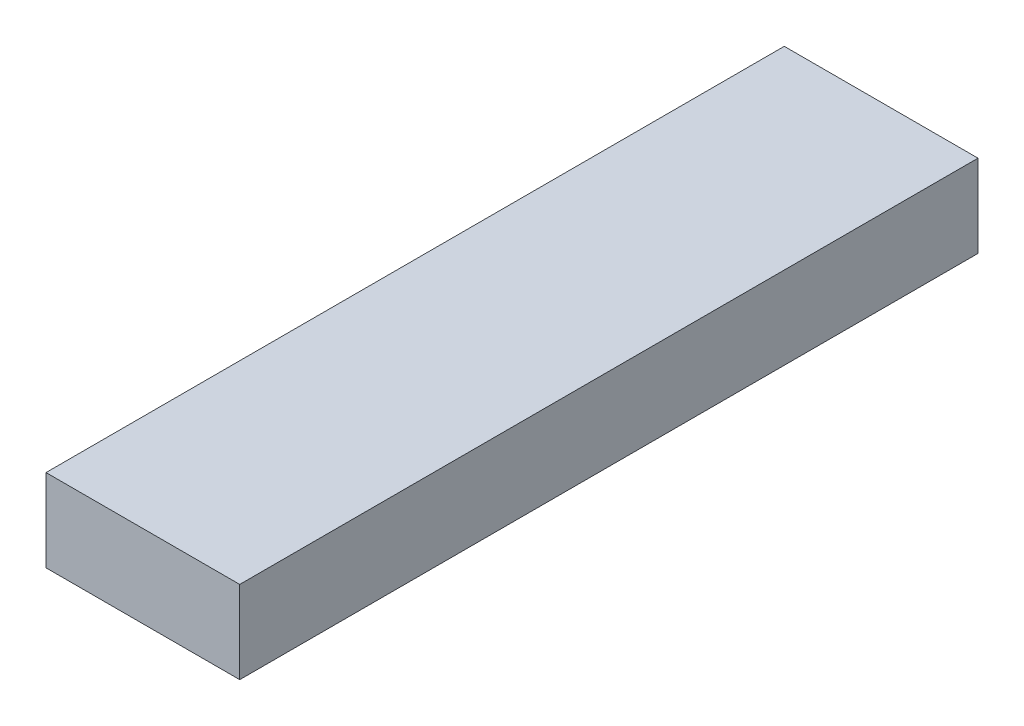
SolidWorks part; units mm, degrees
ref_plane "Ebene vorne" through (0, 0, 0) normal (0, 0, 1) x (1, 0, 0)
ref_plane "Ebene oben" through (0, 0, 0) normal (0, 1, 0) x (1, 0, 0)
ref_plane "Ebene rechts" through (0, 0, 0) normal (1, 0, 0) x (0, 0, -1)
sketch "Skizze1" plane through (0, 0, 0) normal (0, 0, 1) x (1, 0, 0)
  line L0 (-136.0693, 146.6266) -> (-136.0693, 124.273) construction
  line L1 (-188.5516, 124.273) -> (-136.0693, 124.273) construction
  line L2 (-188.5516, 146.6266) -> (-188.5516, 124.273) construction
  line L3 (-188.5516, 146.6266) -> (-136.0693, 146.6266) construction
  line L4 (-136.0693, 146.6266) -> (-136.0693, 124.273)
  line L5 (-188.5516, 124.273) -> (-136.0693, 124.273)
  line L6 (-188.5516, 146.6266) -> (-188.5516, 124.273)
  line L7 (-188.5516, 146.6266) -> (-136.0693, 146.6266)
extrude "Aufsatz-Linear austragen1" add sketch "Skizze1" along normal blind 200
